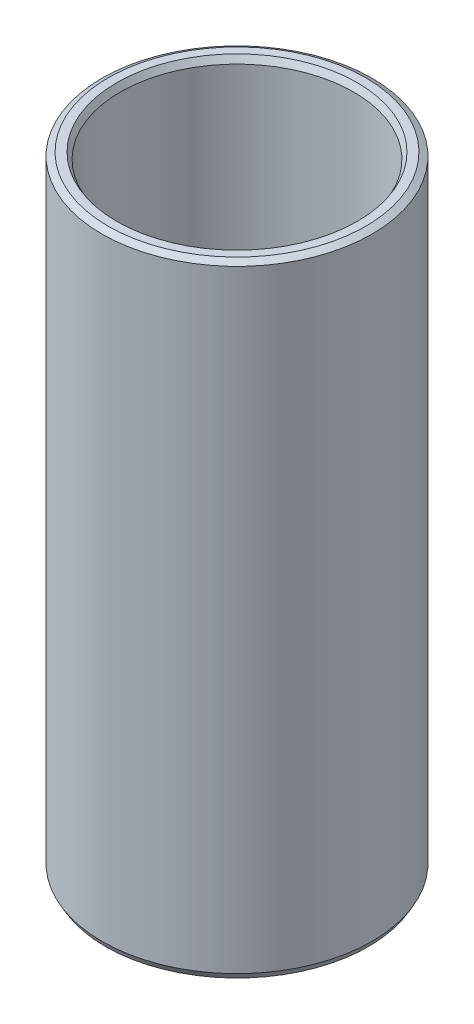
SolidWorks part; units mm, degrees
ref_plane "Front Plane" through (0, 0, 0) normal (0, 0, 1) x (1, 0, 0)
ref_plane "Top Plane" through (0, 0, 0) normal (0, 1, 0) x (1, 0, 0)
ref_plane "Right Plane" through (0, 0, 0) normal (1, 0, 0) x (0, 0, -1)
sketch "Sketch1" plane through (0, 0, 0) normal (0, 1, 0) x (1, 0, 0)
  circle A0 centre (0, 0) radius 47.5
  dimension "SLEEVE_OD" = 95
extrude "Boss-Extrude1" add sketch "Sketch1" along normal blind 218.951
sketch "Sketch2" plane through (0, 0, 0) normal (0, 1, 0) x (1, 0, 0)
  circle A0 centre (0, 0) radius 41.0344
  dimension "BORE_D" = 82.0688
extrude "Cut-Extrude1" cut sketch "Sketch2" along normal through all
chamfer "Chamfer1" distance 1.2562 angle 60.586 4 edges at (0, 218.951, 41.0344) (0, 0, 41.0344) (0, 0, 47.5) (0, 218.951, 47.5) first distance on face at (0, 218.951, 41.0344) first distance on face at (0, 0, 41.0344) first distance on face at (0, 218.951, 47.5)
